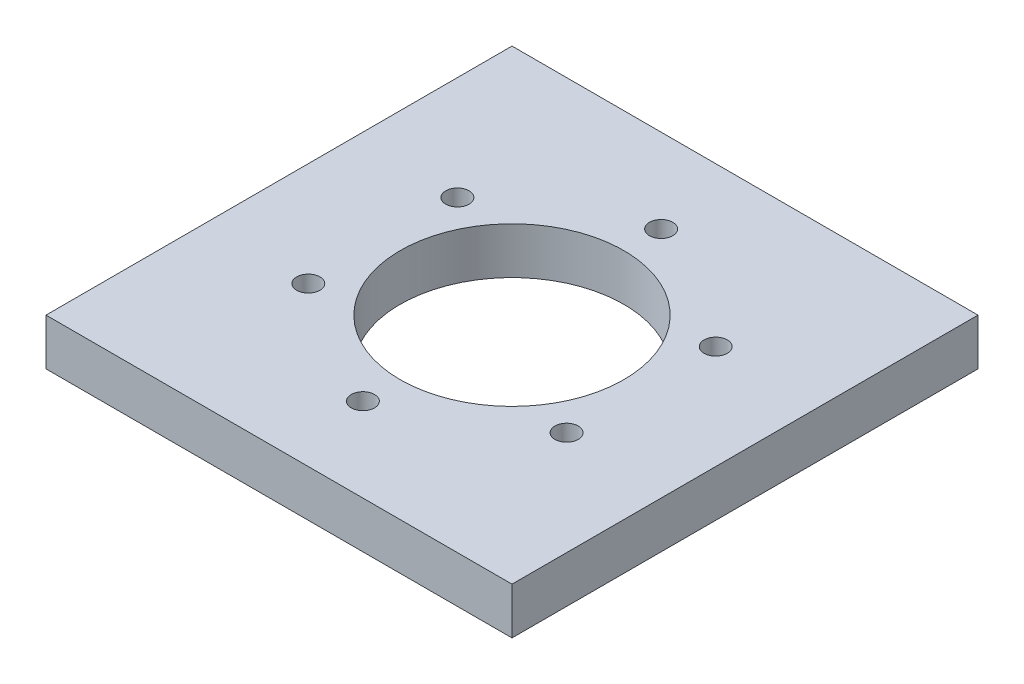
SolidWorks part; units mm, degrees
ref_plane "Front Plane" through (0, 0, 0) normal (0, 0, 1) x (1, 0, 0)
ref_plane "Top Plane" through (0, 0, 0) normal (0, 1, 0) x (1, 0, 0)
ref_plane "Right Plane" through (0, 0, 0) normal (1, 0, 0) x (0, 0, -1)
sketch "Sketch2" plane through (0, 0, 0) normal (0, 1, 0) x (1, 0, 0)
  line L1 (-18.6933, 24.1456) -> (31.3067, 24.1456)
  line L2 (-18.6933, 24.1456) -> (-18.6933, -25.8544)
  line L3 (-18.6933, -25.8544) -> (31.3067, -25.8544)
  line L4 (31.3067, 24.1456) -> (31.3067, -25.8544)
  circle A0 centre (6.3067, -0.8544) radius 12
  point P4 (6.3067, -0.8544)
  dimension "D1" = 24
  dimension "D2" = 50
  dimension "D3" = 50
extrude "Boss-Extrude1" add sketch "Sketch2" along normal blind 5
sketch "Sketch4" plane through (0, 5, 0) normal (0, 1, 0) x (1, 0, 0)
  circle A0 centre (6.3067, 15.1456) radius 1.25 construction
  circle A1 centre (6.3067, 15.1456) radius 1.25
  circle A2 centre (6.3067, -16.8544) radius 1.25 construction
  circle A3 centre (6.3067, -16.8544) radius 1.25
  circle A4 centre (-7.5497, -8.8544) radius 1.25 construction
  circle A5 centre (-7.5497, -8.8544) radius 1.25
  circle A6 centre (-7.5497, -8.8544) radius 1.25 construction
  circle A7 centre (-7.5497, -8.8544) radius 1.25
  circle A8 centre (-7.5497, 7.1456) radius 1.25 construction
  circle A9 centre (-7.5497, 7.1456) radius 1.25
  circle A10 centre (20.1631, 7.1456) radius 1.25 construction
  circle A11 centre (20.1631, 7.1456) radius 1.25
  circle A12 centre (20.1631, -8.8544) radius 1.25 construction
  circle A13 centre (20.1631, -8.8544) radius 1.25
  point P20 (0, 0)
sketch "Sketch5" plane through (0, 5, 0) normal (0, 1, 0) x (1, 0, 0)
  circle A0 centre (6.3067, 15.1456) radius 1.25
  circle A1 centre (20.1631, 7.1456) radius 1.25
  circle A2 centre (20.1631, -8.8544) radius 1.25
  circle A4 centre (6.3067, -16.8544) radius 1.25
  circle A5 centre (-7.5497, -8.8544) radius 1.25
  circle A6 centre (-7.5497, 7.1456) radius 1.25
  dimension "D1" = 2.5
  dimension "D2" = 2.5
  dimension "D3" = 2.5
  dimension "D4" = 2.5
  dimension "D5" = 2.5
  dimension "D6" = 2.5
extrude "Cut-Extrude1" cut sketch "Sketch5" against normal blind 6
